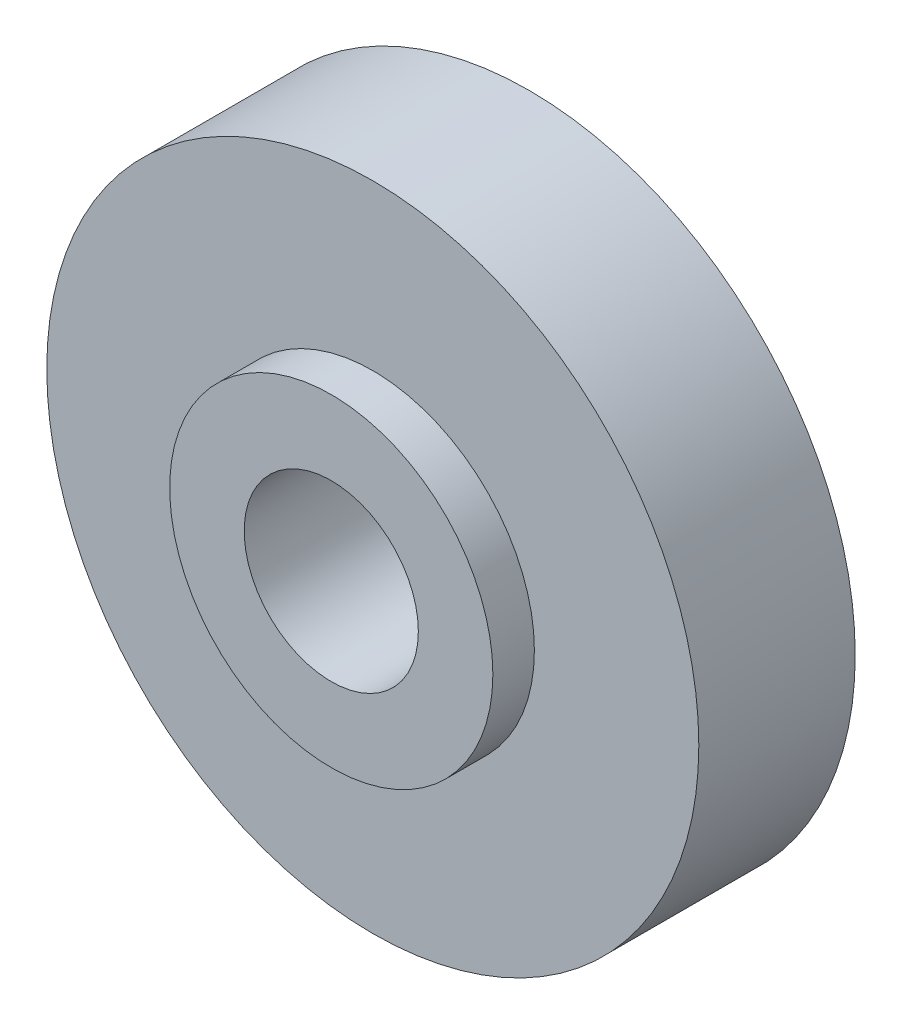
SolidWorks part; units mm, degrees
ref_plane "Front Plane" through (0, 0, 0) normal (0, 0, 1) x (1, 0, 0)
ref_plane "Top Plane" through (0, 0, 0) normal (0, 1, 0) x (1, 0, 0)
ref_plane "Right Plane" through (0, 0, 0) normal (1, 0, 0) x (0, 0, -1)
sketch "Sketch1" plane through (0, 0, 0) normal (0, 0, 1) x (1, 0, 0)
  circle A0 centre (0, 0) radius 24.7269
  circle A1 centre (0, 0) radius 6.604
  circle A2 centre (0, 0) radius 12.2555
  dimension "D1" = 49.4538
  dimension "D2" = 13.208
  dimension "D3" = 24.511
extrude "Boss-Extrude1" add sketch "Sketch1" along normal mid plane 11.8618 contours A0 A2 region at (-24.0275, 0, 0)
extrude "Boss-Extrude2" add sketch "Sketch1<3>" along normal mid plane 18.161 separate body contours A2 A1 region at (-11.9089, 0, 0)
sketch "Sketch1<3>" plane through (0, 0, 0) normal (0, 0, 1) x (1, 0, 0) same geometry as "Sketch1"
